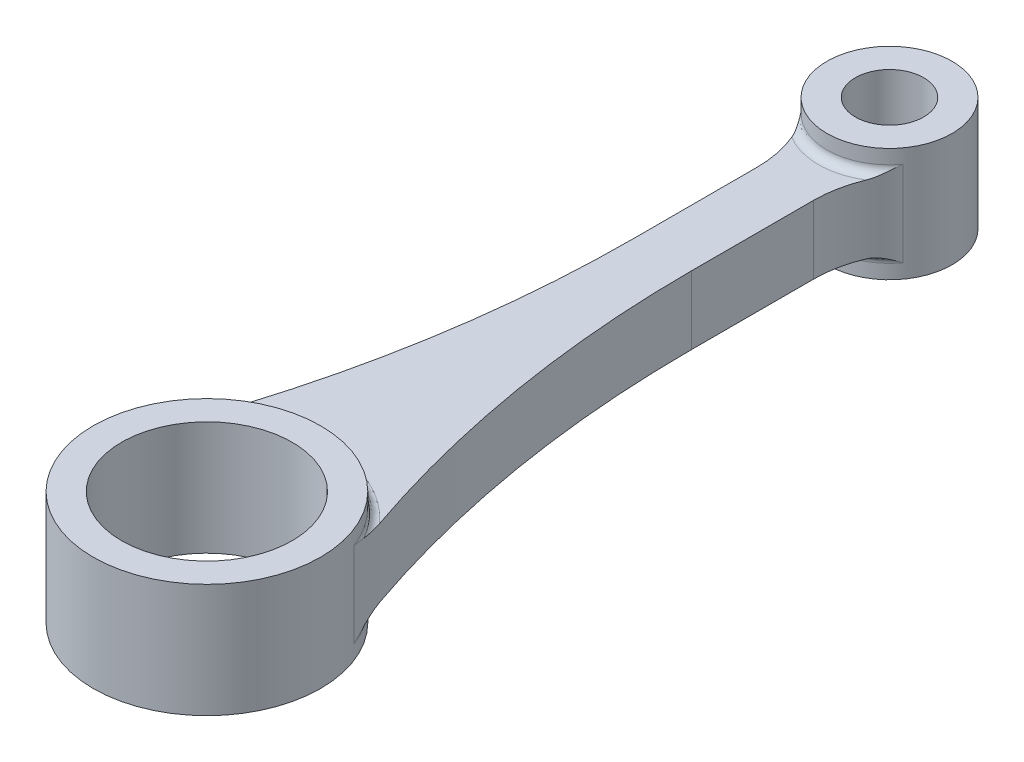
SolidWorks part; units mm, degrees
ref_plane "Płaszczyzna przednia" through (0, 0, 0) normal (0, 0, 1) x (1, 0, 0)
ref_plane "Płaszczyzna górna" through (0, 0, 0) normal (0, 1, 0) x (1, 0, 0)
ref_plane "Płaszczyzna prawa" through (0, 0, 0) normal (1, 0, 0) x (0, 0, -1)
sketch "Szkic1" plane through (0, 0, 0) normal (0, 1, 0) x (1, 0, 0)
  circle A0 centre (0, 0) radius 15
  circle A1 centre (0, 0) radius 20
  circle A2 centre (0, 120) radius 6
  circle A3 centre (0, 120) radius 11
  point P7 (0, 0)
  point P8 (0, 0)
  point P9 (0, 0)
  dimension "D1" = 30
  dimension "D2" = 40
  dimension "D3" = 12
  dimension "D4" = 22
  dimension "D5" = 120
extrude "Dodanie-wyciągnięcie1" add sketch "Szkic1" along normal mid plane 20
sketch "Szkic2" plane through (0, 0, 0) normal (0, 1, 0) x (1, 0, 0)
  line L0 (5, 110.202) -> (5, 80.202)
  line L1 (-5, 110.202) -> (-5, 80.202)
  circle A0 centre (0, 120) radius 11 construction
  arc A1 (5, 80.202) -> (18.6481, 7.2283) centre (206.9122, 80.202) ccw
  circle A2 centre (0, 0) radius 20 construction
  arc A3 (-5, 80.202) -> (-18.6481, 7.2283) centre (-206.9122, 80.202) cw
  arc A4 (-5, 110.202) -> (5, 110.202) centre (0, 120) ccw
  arc A5 (-18.6481, 7.2283) -> (18.6481, 7.2283) centre (0, 0) cw
  dimension "D1" = 30
  dimension "D2" = 5
  dimension "D3" = 10
extrude "Dodanie-wyciągnięcie2" add sketch "Szkic2" along normal mid plane 12
fillet "Zaokrąglenie1" radius 1.5 1 edges at (0, 6, -109)
fillet "Zaokrąglenie2" radius 1.5 1 edges at (0, 6, -20)
fillet "Zaokrąglenie3" radius 1.5 1 edges at (0, -6, -20)
fillet "Zaokrąglenie4" radius 1.5 1 edges at (0, -6, -109)
fillet "Zaokrąglenie5" radius 20 1 edges at (5, 0, -110.202)
fillet "Zaokrąglenie6" radius 20 1 edges at (-5, 0, -110.202)
